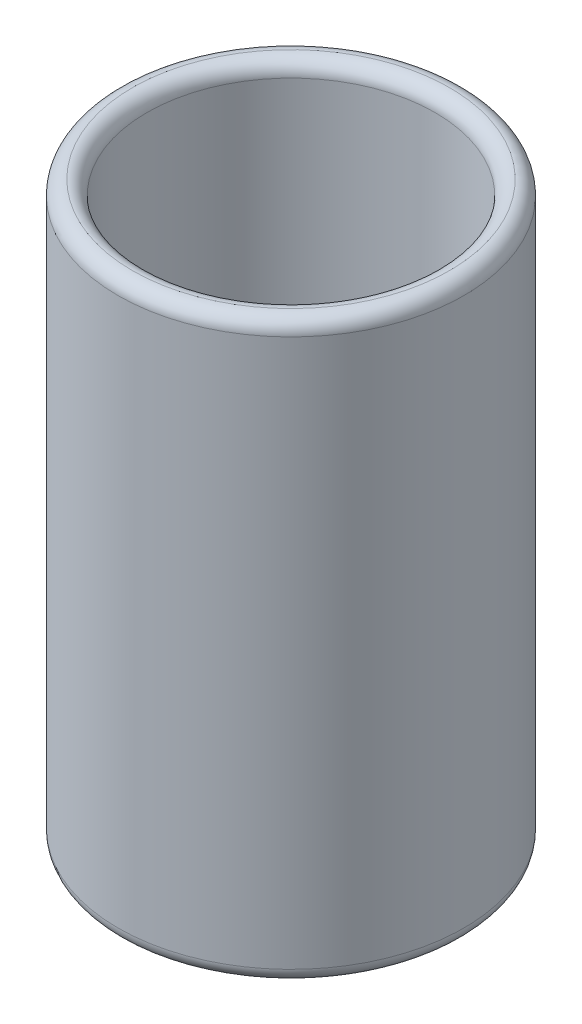
SolidWorks part; units mm, degrees
material "Cast Stainless Steel"
ref_plane "Front Plane" through (0, 0, 0) normal (0, 0, 1) x (1, 0, 0)
ref_plane "Top Plane" through (0, 0, 0) normal (0, 1, 0) x (1, 0, 0)
ref_plane "Right Plane" through (0, 0, 0) normal (1, 0, 0) x (0, 0, -1)
sketch "Sketch2" plane through (0, 0, 0) normal (0, 1, 0) x (1, 0, 0)
  circle A0 centre (0, 0) radius 5
  circle A1 centre (0, 0) radius 6
  dimension "D1" = 12
  dimension "D2" = 10
extrude "Boss-Extrude1" add sketch "Sketch2" along normal blind 20
fillet "Fillet1" radius 0.5 4 edges at (0, 0, 5) (0, 0, 6) (0, 20, 5) (0, 20, 6)
